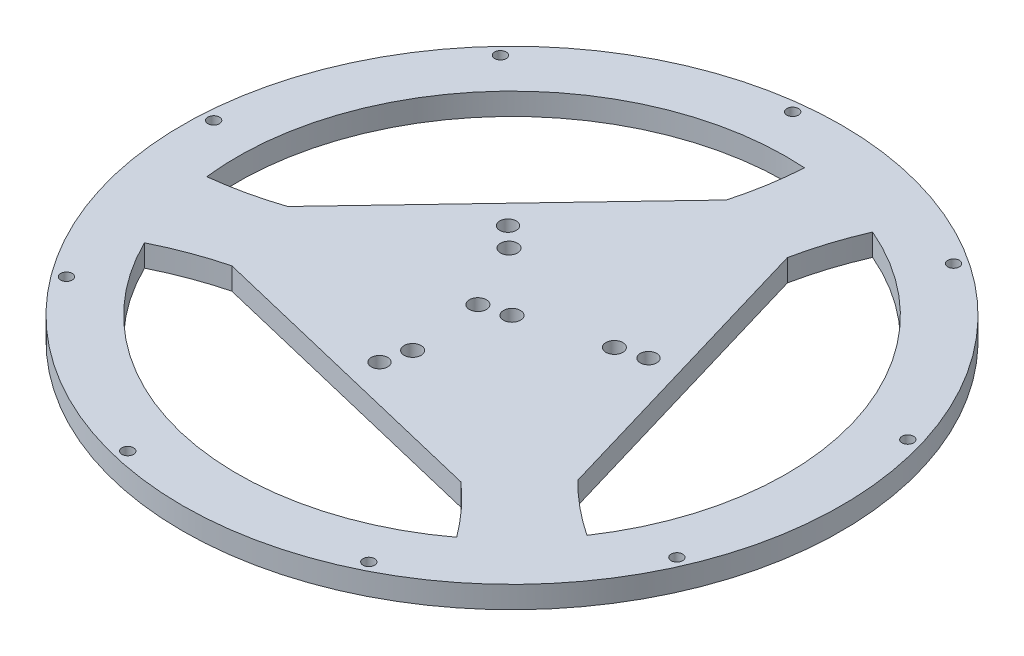
SolidWorks part; units mm, degrees
note: The reader was unsure of these and kept them because the rebuilt part matched: shared geometry of "草图3<17>", "草图3<22>", "草图3<23>".
ref_plane "前视基准面" through (0, 0, 0) normal (0, 0, 1) x (1, 0, 0)
ref_plane "上视基准面" through (0, 0, 0) normal (0, 1, 0) x (1, 0, 0)
ref_plane "右视基准面" through (0, 0, 0) normal (1, 0, 0) x (0, 0, -1)
other "Configuration Table"
sketch "草图3" plane through (0, 0, 0) normal (0, 1, 0) x (1, 0, 0)
  line L0 (0, 0) -> (-18.1254, 17.2183) construction
  line L1 (1.3258, 37.6943) -> (-37.5767, -3.2578)
  line L2 (-33.3071, -17.699) -> (21.6096, -30.9135)
  line L3 (31.9813, -19.9953) -> (15.967, 34.1712)
  line L4 (-18.1254, 17.2183) -> (-56.5061, 53.678) construction
  line L5 (0, 0) -> (-4.679, -19.445) construction
  line L7 (-14.5003, 13.7746) -> (0, 0) construction
  line L9 (0, 0) -> (19.1793, 5.6704) construction
  circle A2 centre (0, 0) radius 60
  arc A3 (3.374, 49.886) -> (-49.6473, -5.9287) centre (0, 0) ccw
  circle A4 centre (0, 0) radius 25 construction
  arc A6 (-49.6473, -5.9287) -> (-37.5767, -3.2578) centre (-56.5061, 53.678) ccw
  arc A7 (1.3258, 37.6943) -> (3.374, 49.886) centre (-56.5061, 53.678) ccw
  arc A8 (19.6892, 45.9601) -> (15.967, 34.1712) centre (74.7395, 22.0967) ccw
  arc A9 (31.9813, -19.9953) -> (41.5156, -27.865) centre (74.7395, 22.0967) ccw
  arc A10 (29.958, -40.0314) -> (21.6096, -30.9135) centre (-18.2335, -75.7747) ccw
  arc A11 (-33.3071, -17.699) -> (-44.8896, -22.021) centre (-18.2335, -75.7747) ccw
  arc A12 (41.5156, -27.865) -> (19.6892, 45.9601) centre (0, 0) ccw
  arc A13 (-44.8896, -22.021) -> (29.958, -40.0314) centre (0, 0) ccw
  circle A14 centre (-14.5003, 13.7746) radius 1.5
  circle A15 centre (19.1793, 5.6704) radius 1.5
  circle A16 centre (-4.679, -19.445) radius 1.5
  circle A17 centre (-42.051, 39.9464) radius 1.0529
  circle A26 centre (0, 0) radius 1.55
  circle A27 centre (-6.5359, 57.6306) radius 1.0529
  circle A28 centre (32.0374, 48.3488) radius 1.0529
  circle A29 centre (55.6201, 16.444) radius 1.0529
  circle A30 centre (53.1775, -23.155) radius 1.0529
  circle A31 centre (25.8526, -51.9196) radius 1.0529
  circle A32 centre (-13.5691, -56.3904) radius 1.0529
  circle A33 centre (-46.6416, -34.4755) radius 1.0529
  circle A34 centre (-57.89, 3.5708) radius 1.0529
  circle A37 centre (-3.5092, -14.5837) radius 1.55
  circle A38 centre (-10.8753, 10.331) radius 1.55
  circle A39 centre (14.3845, 4.2528) radius 1.55
  circle A40 centre (-4.7948, -1.4176) radius 1.55
  point P3 (-18.1254, 17.2183)
  point P11 (1.3258, 37.6943)
  point P12 (-37.5767, -3.2578)
  point P13 (-49.6473, -5.9287)
  point P14 (-59.6748, -6.2383)
  point P15 (3.1688, 59.9163)
  point P16 (3.374, 49.886)
  point P34 (0, 0)
  point P38 (0, 0)
  point P59 (0, 0)
  dimension "D1" = 120
  dimension "D2" = 100
  dimension "D5" = 60
  dimension "D6" = 56.9357
  dimension "D8" = 16.7809
  dimension "D10" = 3
  dimension "D15" = 2.1059
  dimension "D19" = 3.1
  dimension "D21" = 3.1
  dimension "D23" = 3.1
  dimension "D25" = 3.1
  dimension "D27" = 3.1
  dimension "D3" = 20
  dimension "D4" = 25
  dimension "D7" = 3
  dimension "D9" = 45.9601
  dimension "D12" = 19.445
  dimension "D13" = 19.1793
  dimension "D14" = 58
  dimension "D17" = 36.3755
  dimension "D18" = 12.5771
  dimension "D20" = 5
  dimension "D22" = 5
  dimension "D24" = 5
  dimension "D26" = 5
  dimension "D11" = 3
  dimension "D16" = 9
extrude "凸台-拉伸4" add sketch "草图3" along normal blind 4
extrude "切除-拉伸15" cut sketch "草图3<17>" along normal blind 4 contours L1 A7 A3 A6
sketch "草图3<17>" plane through (0, 0, 0) normal (0, 1, 0) x (1, 0, 0) same geometry as "草图3"
extrude "切除-拉伸23" cut sketch "草图3<22>" along normal blind 10 contours A26
sketch "草图3<22>" plane through (0, 0, 0) normal (0, 1, 0) x (1, 0, 0) same geometry as "草图3"
extrude "切除-拉伸24" cut sketch "草图3<23>" along normal blind 10 contours A34
sketch "草图3<23>" plane through (0, 0, 0) normal (0, 1, 0) x (1, 0, 0) same geometry as "草图3"
